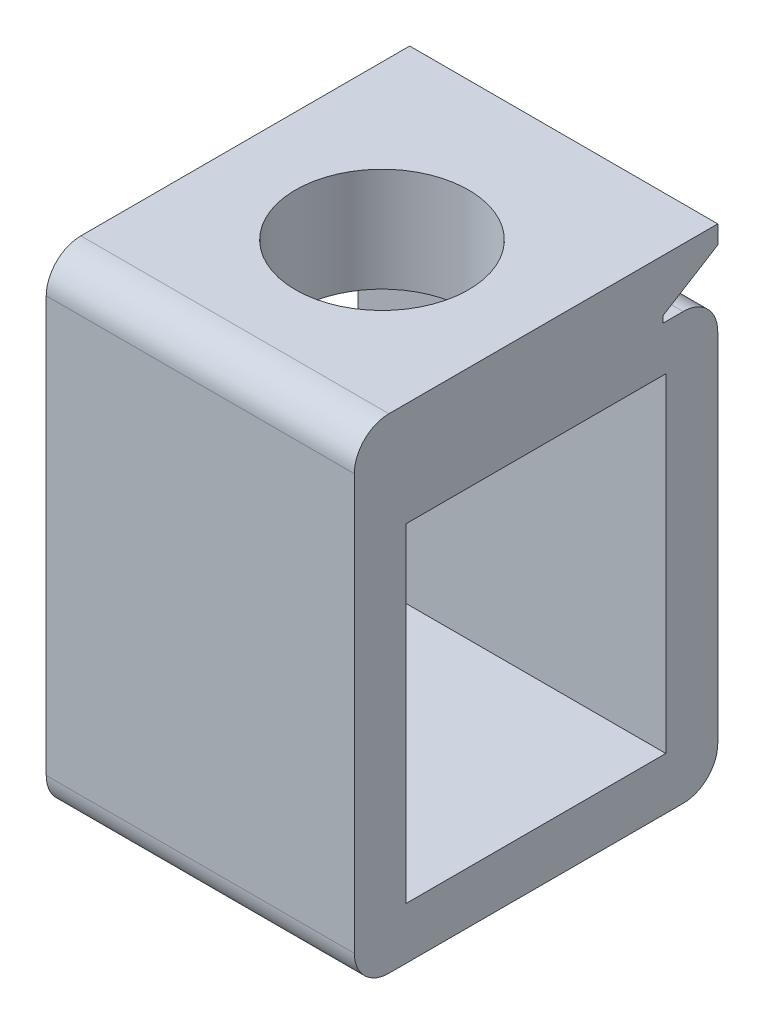
SolidWorks part; units mm, degrees
ref_plane "前视基准面" through (0, 0, 0) normal (0, 0, 1) x (1, 0, 0)
ref_plane "上视基准面" through (0, 0, 0) normal (0, 1, 0) x (1, 0, 0)
ref_plane "右视基准面" through (0, 0, 0) normal (1, 0, 0) x (0, 0, -1)
sketch "草图1" plane through (0, 0, 0) normal (1, 0, 0) x (0, 0, -1)
  line L0 (0, 55.2081) -> (0, -65.0723) construction
  line L1 (-5.25, 7) -> (5.25, 7)
  line L2 (-5.25, 7) -> (-5.25, -7)
  line L3 (-5.25, -7) -> (5.25, -7)
  line L4 (5.25, 7) -> (5.25, -7)
  line L5 (-64.7541, 0) -> (63.7995, 0) construction
  line L7 (3.75, -5.5) -> (-3.75, -5.5)
  line L8 (3.75, -5.5) -> (3.75, 4)
  line L9 (3.75, 4) -> (-3.75, 4)
  line L10 (-3.75, -5.5) -> (-3.75, 4)
  dimension "D1" = 14
  dimension "D2" = 10.5
  dimension "D3" = 1.5
  dimension "D4" = 3
  dimension "D5" = 1.5
  dimension "D6" = 1.5
extrude "凸台-拉伸1" add sketch "草图1" along normal blind 4.45 and the other way blind 4.45
sketch "草图2" plane through (0, 7, 0) normal (0, 1, 0) x (1, 0, 0)
  circle A0 centre (0, 0) radius 2.5
  dimension "D1" = 5
extrude "切除-拉伸1" cut sketch "草图2" against normal blind 5
sketch "草图3" plane through (4.45, 0, 0) normal (1, 0, 0) x (0, 0, -1)
  line L0 (5.25, 6.471) -> (3.6611, 5.4904)
  line L1 (5.25, -7) -> (5.25, 7) construction
  line L2 (3.6611, 5.4904) -> (3.6611, 5.3065)
  line L3 (3.6611, 5.3065) -> (5.25, 5.3065)
extrude "切除-拉伸2" cut sketch "草图3" against normal through all and the other way through all
fillet "圆角1" radius 1 4 edges at (0, -7, -5.25) (0, -7, 5.25) (0, 7, 5.25) (0, 5.3065, -5.25)
